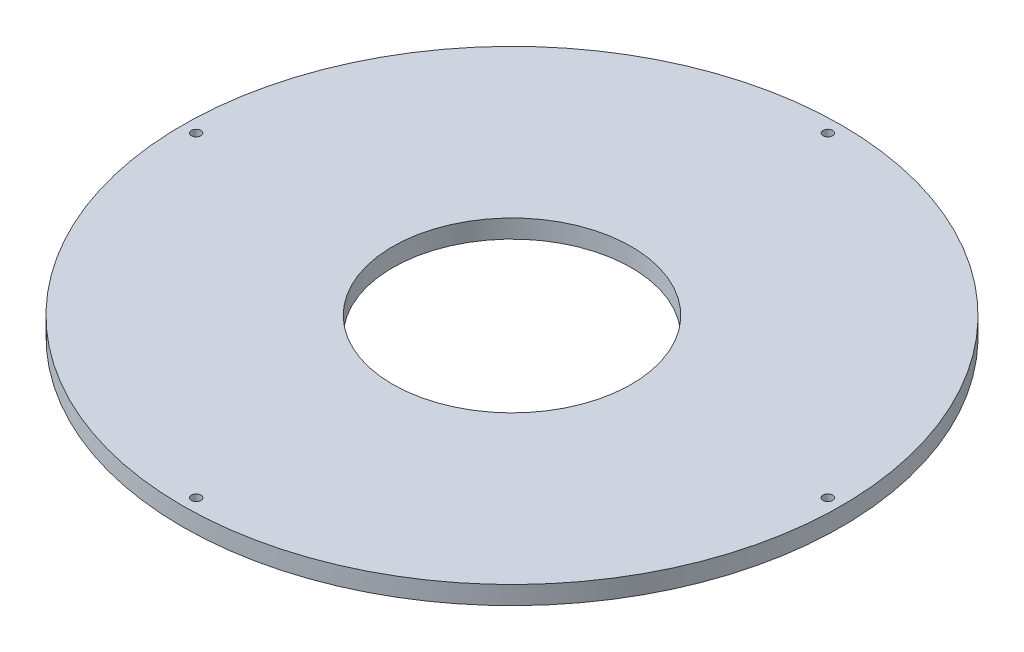
SolidWorks part; units mm, degrees
material "Acrylic (Medium-high impact)"
ref_plane "Front Plane" through (0, 0, 0) normal (0, 0, 1) x (1, 0, 0)
ref_plane "Top Plane" through (0, 0, 0) normal (0, 1, 0) x (1, 0, 0)
ref_plane "Right Plane" through (0, 0, 0) normal (1, 0, 0) x (0, 0, -1)
sketch "Sketch1" plane through (0, 0, 0) normal (0, 1, 0) x (1, 0, 0)
  circle A0 centre (0, 0) radius 41.402
  circle A1 centre (0, 0) radius 114.3
  dimension "D1" = 82.804
  dimension "D2" = 228.6
extrude "Boss-Extrude1" add sketch "Sketch1" along normal blind 6.35
hole_wizard "#4 Clearance Hole1" positions "Sketch2" profile "Sketch3" hole size "#4" standard "ANSI Inch" end condition through all
sketch "Sketch2" plane through (0, 6.35, 0) normal (0, 1, 0) x (1, 0, 0)
  circle A0 centre (0, 0) radius 109.5375
  circle A1 centre (0, 0) radius 114.3 construction
  point P7 (0, 109.5375)
  point P9 (109.5375, 0)
  point P11 (0, -109.5375)
  point P13 (-109.5375, 0)
  dimension "D1" = 4.7625
sketch "Sketch3" plane through (0, 6.35, -109.5375) normal (1, 0, 0) x (0, 0, 1)
  line L0 (0, 0) -> (0, 6.35)
  line L1 (0, 6.35) -> (1.6319, 6.35)
  line L2 (1.6319, 6.35) -> (1.6319, 0)
  line L5 (1.6319, 0) -> (0, 0)
  line L11 (0, -6.35) -> (0, 107.95) construction
  dimension "Thru Hole Dia." = 3.2639
  dimension "Thru Hole Depth" = 6.35
